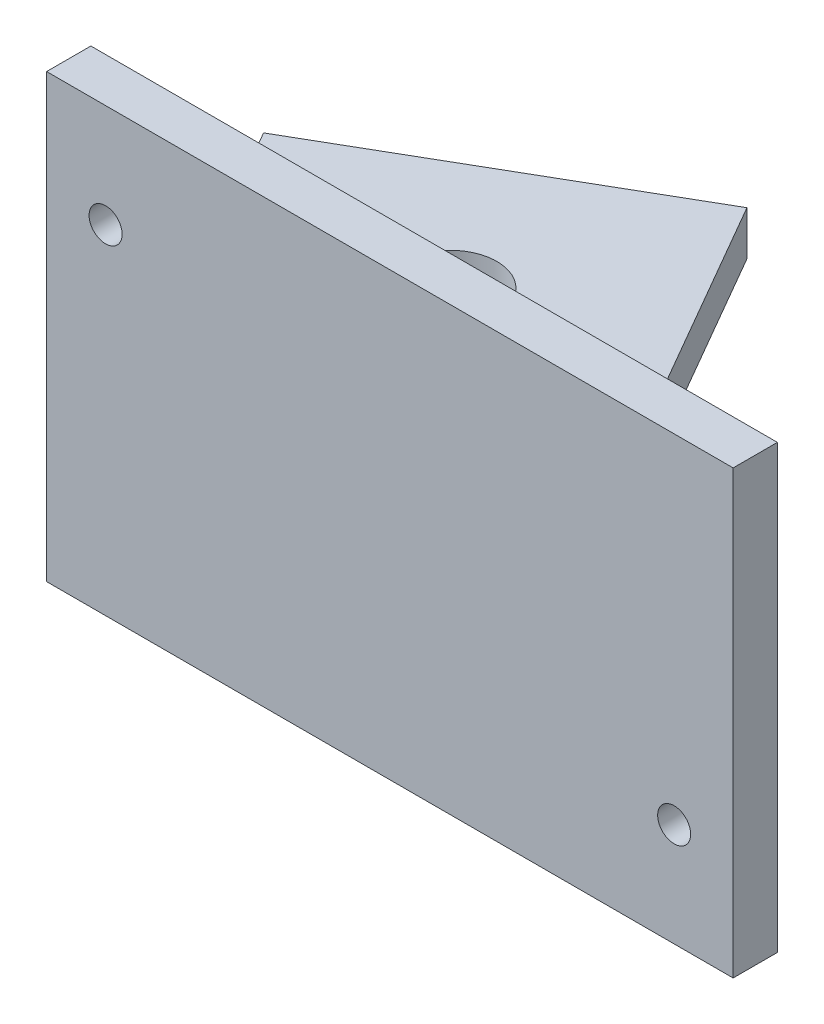
SolidWorks part; units mm, degrees
ref_plane "Front Plane" through (0, 0, 0) normal (0, 0, 1) x (1, 0, 0)
ref_plane "Top Plane" through (0, 0, 0) normal (0, 1, 0) x (1, 0, 0)
ref_plane "Right Plane" through (0, 0, 0) normal (1, 0, 0) x (0, 0, -1)
sketch "Sketch1" plane through (0, 0, 0) normal (0, 0, 1) x (1, 0, 0)
  line L1 (0, 0) -> (33.782, 0) construction
  line L2 (0, 0) -> (0, 19.812) construction
  line L3 (0, 19.812) -> (33.782, 19.812) construction
  line L4 (33.782, 0) -> (33.782, 19.812) construction
  line L5 (-1.5875, -1.5875) -> (35.3695, -1.5875)
  line L6 (-1.5875, -1.5875) -> (-1.5875, 19.812)
  line L7 (-1.5875, 19.812) -> (35.3695, 19.812)
  line L8 (35.3695, -1.5875) -> (35.3695, 19.812)
  circle A0 centre (1.5875, 14.2558) radius 0.889
  circle A1 centre (32.1945, 1.5875) radius 0.889
  dimension "D3" = 1.778
  dimension "D4" = 1.778
  dimension "D5" = 1.5875
  dimension "D6" = 1.5875
  dimension "D7" = 1.5875
  dimension "D8" = 5.5562
  dimension "D9" = 3.175
  dimension "D11" = 3.175
  dimension "D12" = 5.5562
  dimension "D1" = 19.812
  dimension "D2" = 33.782
  dimension "D10" = 3.175
extrude "Boss-Extrude1" add sketch "Sketch1" along normal blind 2.3813
sketch "Sketch2" plane through (0, -1.5875, 0) normal (0, -1, 0) x (1, 0, 0)
  line L8 (-1.5875, 0) -> (20.4095, 0) construction
  line L9 (-1.5875, 2.3813) -> (35.3695, 2.3813)
  line L10 (-1.5875, 2.3813) -> (-1.5875, 0)
  line L12 (35.3695, 2.3813) -> (35.3695, 0)
  line L15 (2.2103, -31.522) -> (-14.2875, -21.997)
  line L16 (-1.5875, 0) -> (-14.2875, -21.997)
  line L17 (2.2103, -31.522) -> (20.4095, 0)
  line L18 (20.4095, 0) -> (35.3695, 0)
  dimension "D1" = 19.05
  dimension "D2" = 60
  dimension "D3" = 25.4
extrude "Boss-Extrude3" add sketch "Sketch2" along normal blind 2.3813
sketch "Sketch4" plane through (0, -1.5875, 0) normal (0, 1, 0) x (1, 0, 0)
  line L0 (-6.0386, 26.7595) -> (-2.019, 19.7973) construction
  line L1 (-14.2875, 21.997) -> (2.2103, 31.522) construction
  line L2 (-2.019, 19.7973) -> (4.331, 8.7988) construction
  line L3 (4.331, 8.7988) -> (9.411, 0) construction
  line L4 (-1.5875, 0) -> (20.4095, 0) construction
  circle A0 centre (-2.019, 19.7973) radius 2.4892
  circle A1 centre (4.331, 8.7988) radius 2.4892
  dimension "D1" = 4.9784
  dimension "D2" = 12.7
  dimension "D3" = 10.16
extrude "Cut-Extrude2" cut sketch "Sketch4" against normal up to next
